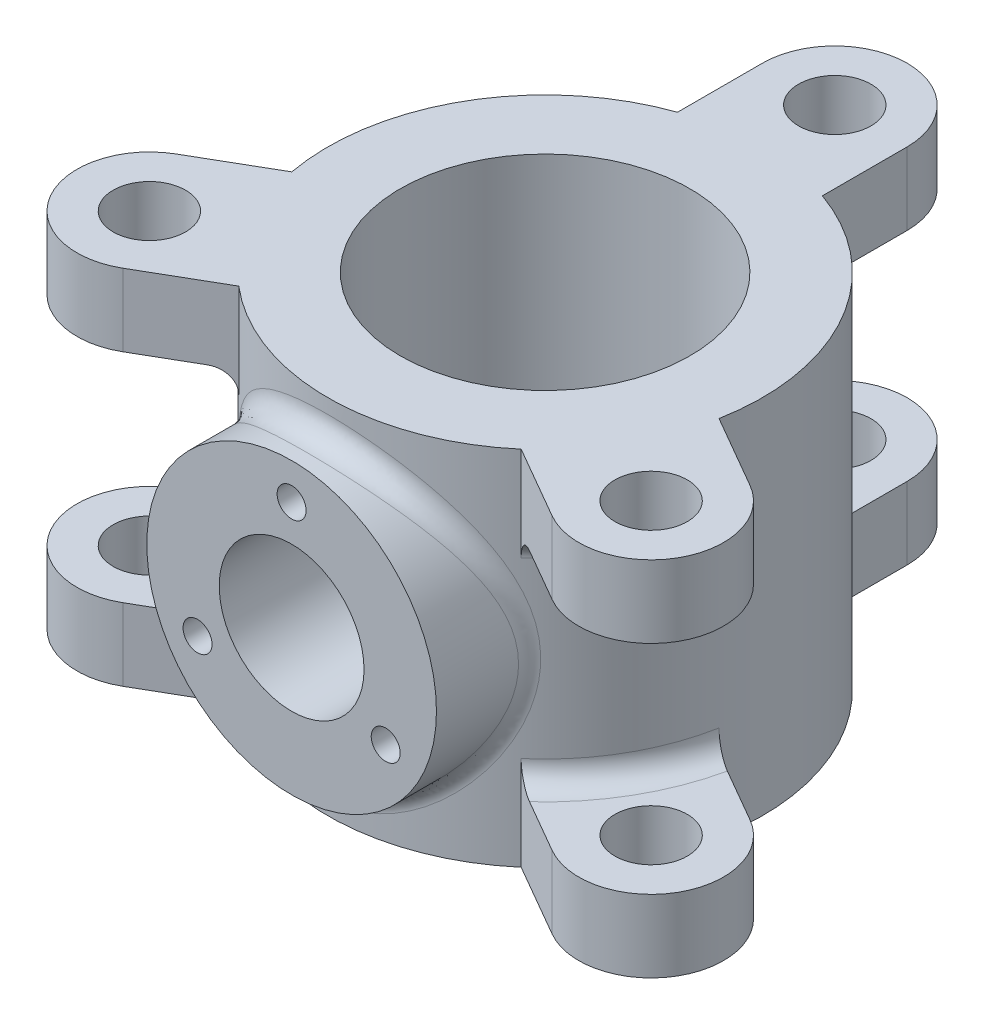
SolidWorks part; units mm, degrees
note: The reader was unsure of these and kept them because the rebuilt part matched: shared geometry of "Sketch1<3>", "Sketch2<2>".
material "1060 Alloy"
ref_plane "Front Plane" through (0, 0, 0) normal (0, 0, 1) x (1, 0, 0)
ref_plane "Top Plane" through (0, 0, 0) normal (0, 1, 0) x (1, 0, 0)
ref_plane "Right Plane" through (0, 0, 0) normal (1, 0, 0) x (0, 0, -1)
sketch "Sketch1" plane through (0, 0, 0) normal (0, 1, 0) x (1, 0, 0)
  line L0 (0, 0) -> (0, 53.931) construction
  line L3 (-10, 28.2843) -> (-10, 40)
  line L5 (10, 28.2843) -> (10, 40)
  circle A0 centre (0, 0) radius 30
  circle A1 centre (0, 0) radius 20
  arc A2 (10, 40) -> (-10, 40) centre (0, 40) ccw
  circle A3 centre (0, 40) radius 5
  point P9 (0, 0)
  dimension "D1" = 40
  dimension "D2" = 60
  dimension "D5" = 10
  dimension "D3" = 20
  dimension "D4" = 40
extrude "Boss-Extrude1" add sketch "Sketch1" along normal mid plane 50
extrude "Boss-Extrude2" add sketch "Sketch1<3>" against normal blind 10 from offset 25 contours L0 A0 L5 A2 A3 | A0 L0 A3 A2 L3
sketch "Sketch1<3>" plane through (0, 0, 0) normal (0, 1, 0) x (1, 0, 0) same geometry as "Sketch1"
pattern_circular "CirPattern1" count 3 over 360 about axis through (0, 0, 0) along (0, 1, 0) of "Boss-Extrude2"
mirror "Mirror1" about plane through (0, 0, 0) normal (0, 1, 0) of "CirPattern1", "Boss-Extrude2"
ref_plane "Plane1" through (0, 0, 35) normal (0, 0, 1) x (1, 0, 0)
sketch "Sketch2" plane through (0, 0, 35) normal (0, 0, 1) x (1, 0, 0)
  circle A0 centre (0, 0) radius 20
  circle A1 centre (0, 0) radius 10
  dimension "D1" = 40
  dimension "D2" = 20
extrude "Boss-Extrude3" add sketch "Sketch2" against normal up to surface (12.6393 mm away)
sketch "Sketch3" plane through (0, 0, 35) normal (0, 0, 1) x (1, 0, 0)
  line L0 (0, 0) -> (0, 23.4345) construction
  circle A0 centre (0, 15) radius 2
  dimension "D2" = 4
  dimension "D1" = 15
extrude "Cut-Extrude1" cut sketch "Sketch3" against normal blind 10
pattern_circular "CirPattern2" count 3 over 360 about axis through (0, 0, 0) along (0, 0, 1) of "Cut-Extrude1"
extrude "Cut-Extrude2" cut sketch "Sketch2<2>" against normal blind 40 contours A1
sketch "Sketch2<2>" plane through (0, 0, 35) normal (0, 0, 1) x (1, 0, 0) same geometry as "Sketch2"
fillet "Fillet1" radius 3 7 edges at (0, 15, -30) (-25.9808, 15, 15) (25.9808, 15, 15) (0, -15, -30) (-25.9808, -15, 15) (25.9808, -15, 15) (-19.5647, -4.1499, 22.7425)
